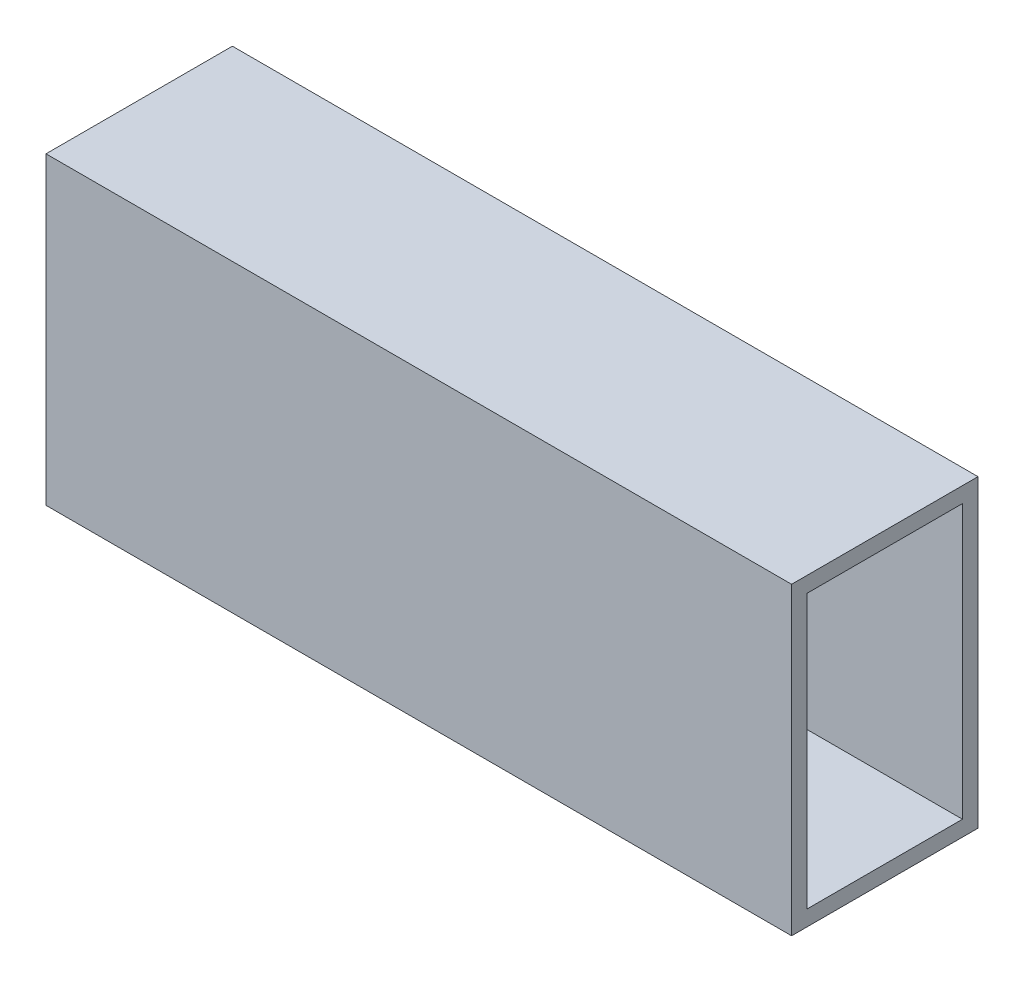
SolidWorks part; units mm, degrees
ref_plane "Front Plane" through (0, 0, 0) normal (0, 0, 1) x (1, 0, 0)
ref_plane "Top Plane" through (0, 0, 0) normal (0, 1, 0) x (1, 0, 0)
ref_plane "Right Plane" through (0, 0, 0) normal (1, 0, 0) x (0, 0, -1)
sketch "Sketch1" plane through (0, 0, 0) normal (0, 1, 0) x (1, 0, 0)
  line L1 (-120, 30) -> (120, 30)
  line L2 (-120, 30) -> (-120, -30)
  line L3 (-120, -30) -> (120, -30)
  line L4 (120, 30) -> (120, -30)
  line L5 (-120, 30) -> (120, -30) construction
  line L6 (-120, -30) -> (120, 30) construction
  point P0 (0, 0)
  dimension "D1" = 60
  dimension "D2" = 240
extrude "Boss-Extrude1" add sketch "Sketch1" along normal blind 5
sketch "Sketch2" plane through (0, 5, 0) normal (0, 1, 0) x (1, 0, 0)
  line L0 (-120, -30) -> (120, -30) construction
  line L1 (-120, 30) -> (-115, 30)
  line L2 (-120, 30) -> (-120, -30)
  line L3 (-120, -30) -> (-115, -30)
  line L4 (-115, 30) -> (-115, -30)
  line L5 (120, -30) -> (120, 30) construction
  line L6 (-115, 30) -> (120, 30)
  line L7 (-115, 30) -> (-115, 25)
  line L8 (-115, 25) -> (120, 25)
  line L9 (120, 30) -> (120, 25)
  line L11 (-115, -30) -> (120, -30)
  line L12 (-115, -30) -> (-115, -25)
  line L13 (-115, -25) -> (120, -25)
  line L14 (120, -30) -> (120, -25)
  line M13 (120, -30) -> (120, 30)
  line M14 (120, 30) -> (-120, 30)
  line M15 (-120, 30) -> (-120, -30)
  line M16 (-120, -30) -> (120, -30)
  dimension "D1" = 5
  dimension "D2" = 5
  dimension "D3" = 5
extrude "Boss-Extrude2" add sketch "Sketch2" along normal blind 88 contours L13 L4 M16 M13 | L4 M14 M15 M16 | L6 L9 L8 L7 region at (-117.5, 5, 0) region at (2.5, 5, 27.5)
extrude "Boss-Extrude3" add sketch "Sketch1<2>" along normal blind 5 from offset 93
sketch "Sketch1<2>" plane through (0, 0, 0) normal (0, 1, 0) x (1, 0, 0) same geometry as "Sketch1"
